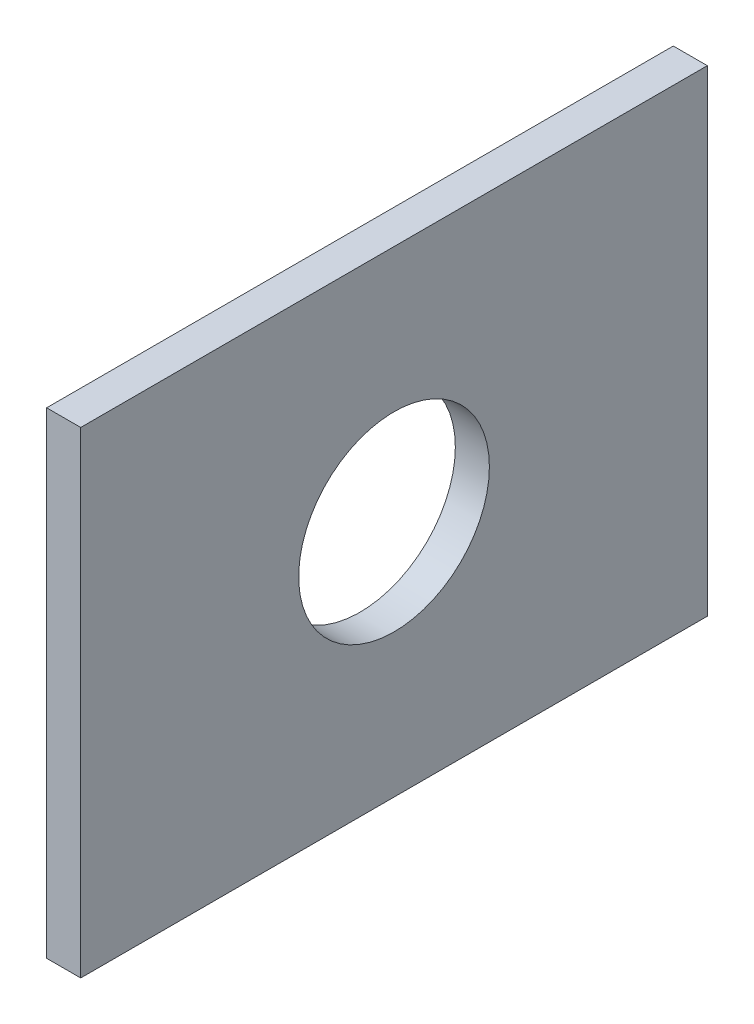
SolidWorks part; units mm, degrees
ref_plane "Front Plane" through (0, 0, 0) normal (0, 0, 1) x (1, 0, 0)
ref_plane "Top Plane" through (0, 0, 0) normal (0, 1, 0) x (1, 0, 0)
ref_plane "Right Plane" through (0, 0, 0) normal (1, 0, 0) x (0, 0, -1)
sketch "Sketch1" plane through (0, 0, 0) normal (1, 0, 0) x (0, 0, -1)
  line L0 (0, 0) -> (92, -70) construction
  line L1 (0, 0) -> (92, 0)
  line L2 (0, 0) -> (0, -70)
  line L3 (0, -70) -> (92, -70)
  line L4 (92, 0) -> (92, -70)
  line L5 (92, 0) -> (0, -70) construction
  line L6 (46, -35) -> (46, 0) construction
  line L7 (46, -17.5) -> (0, -17.5) construction
  circle A0 centre (46, -35) radius 14
  dimension "D3" = 28
  dimension "D1" = 70
  dimension "D2" = 92
extrude "Boss-Extrude1" add sketch "Sketch1" along normal blind 5
